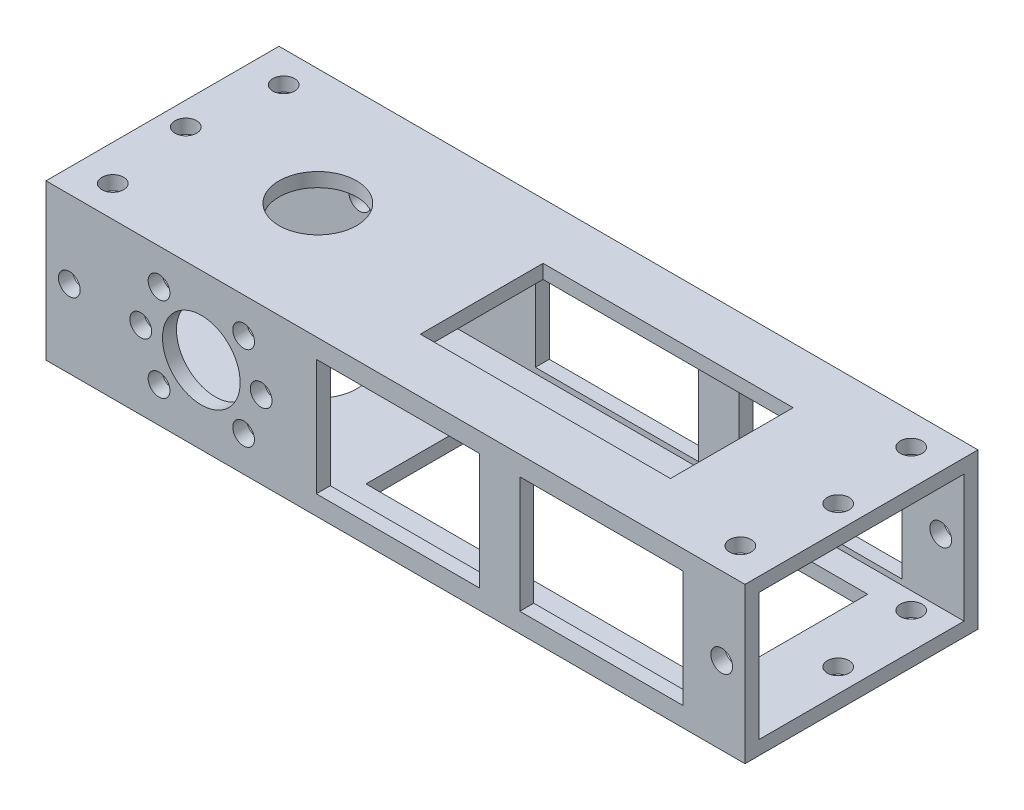
SolidWorks part; units mm, degrees
material "6061-T6 (SS)"
ref_plane "Front Plane" through (0, 0, 0) normal (0, 0, 1) x (1, 0, 0)
ref_plane "Top Plane" through (0, 0, 0) normal (0, 1, 0) x (1, 0, 0)
ref_plane "Right Plane" through (0, 0, 0) normal (1, 0, 0) x (0, 0, -1)
sketch "Sketch1" plane through (0, 0, 0) normal (0, 1, 0) x (1, 0, 0)
  line L1 (0, 0) -> (-114.3, 0)
  line L2 (0, 0) -> (0, -38.1)
  line L3 (0, -38.1) -> (-114.3, -38.1)
  line L4 (-114.3, 0) -> (-114.3, -38.1)
  dimension "D1" = 114.3
  dimension "D2" = 38.1
extrude "Boss-Extrude1" add sketch "Sketch1" along normal blind 25.4
sketch "Sketch2" plane through (0, 0, 0) normal (1, 0, 0) x (0, 0, -1)
  line L0 (0, 0) -> (-2.286, 0) construction
  line L1 (-38.1, 0) -> (0, 0) construction
  line L2 (-2.286, 0) -> (-2.286, 2.286) construction
  line L4 (-2.286, 2.286) -> (-35.814, 2.286)
  line L5 (-2.286, 2.286) -> (-2.286, 23.114)
  line L6 (-2.286, 23.114) -> (-35.814, 23.114)
  line L7 (-35.814, 2.286) -> (-35.814, 23.114)
  line L8 (-38.1, 25.4) -> (-38.1, 0) construction
  point P11 (-38.1, 12.7)
  dimension "D1" = 20.828
  dimension "D2" = 33.528
  dimension "D3" = 2.286
  dimension "D4" = 2.286
extrude "Cut-Extrude1" cut sketch "Sketch2" against normal up to next
sketch "Sketch4" plane through (0, 0, 0) normal (0, 0, -1) x (-1, 0, 0)
  line L0 (0, 0) -> (0, 12.7) construction
  line L1 (0, 25.4) -> (0, 0) construction
  line L2 (0, 12.7) -> (3.81, 12.7) construction
  circle A0 centre (3.81, 12.7) radius 1.778
  dimension "D1" = 3.556
  dimension "D2" = 3.81
extrude "Cut-Extrude3" cut sketch "Sketch4" against normal up to surface (38.1 mm away) up to face at (-57.15, 12.7, 38.1)
sketch "Sketch6" plane through (0, 0, 0) normal (0, 0, -1) x (-1, 0, 0)
  line L0 (114.3, 0) -> (114.3, 12.7) construction
  line L1 (114.3, 25.4) -> (114.3, 0) construction
  line L2 (114.3, 12.7) -> (110.49, 12.7) construction
  line L3 (114.3, 12.7) -> (88.9, 12.7) construction
  line L4 (88.9, 12.7) -> (81.9852, 5.7852) construction
  line L5 (88.9, 12.7) -> (95.8148, 19.6148) construction
  line L6 (88.9, 12.7) -> (95.8148, 5.7852) construction
  line L7 (88.9, 12.7) -> (81.9852, 19.6148) construction
  line L8 (0, 12.7) -> (43.434, 12.7) construction
  line L9 (88.9, 12.7) -> (98.806, 12.7) construction
  line L10 (88.9, 12.7) -> (79.121, 12.7) construction
  line L11 (0, 12.7) -> (10.16, 12.7) construction
  line L12 (0, 25.4) -> (0, 0) construction
  line L13 (10.16, 12.7) -> (10.16, 22.225)
  line L14 (10.16, 22.225) -> (36.83, 22.225)
  line L15 (36.83, 22.225) -> (36.83, 3.175)
  line L16 (36.83, 3.175) -> (10.16, 3.175)
  line L17 (10.16, 3.175) -> (10.16, 12.7)
  line L18 (0, 25.4) -> (114.3, 25.4) construction
  line L19 (43.434, 12.7) -> (43.434, 22.225)
  line L20 (43.434, 22.225) -> (70.104, 22.225)
  line L21 (70.104, 22.225) -> (70.104, 3.175)
  line L22 (70.104, 3.175) -> (43.434, 3.175)
  line L23 (43.434, 3.175) -> (43.434, 12.7)
  circle A0 centre (110.49, 12.7) radius 1.778
  circle A1 centre (88.9, 12.7) radius 6.35
  circle A2 centre (81.9852, 19.6148) radius 1.778
  circle A3 centre (95.8148, 19.6148) radius 1.778
  circle A4 centre (95.8148, 5.7852) radius 1.778
  circle A5 centre (81.9852, 5.7852) radius 1.778
  circle A6 centre (79.121, 12.7) radius 1.778
  circle A7 centre (98.806, 12.7) radius 1.778
  dimension "D1" = 12.7
  dimension "D2" = 3.81
  dimension "D3" = 3.556
  dimension "D5" = 9.779
  dimension "D7" = 9.906
  dimension "D4" = 25.4
  dimension "D6" = 32.3148
  dimension "D8" = 10.16
  dimension "D9" = 26.67
  dimension "D10" = 3.175
  dimension "D11" = 19.05
  dimension "D12" = 43.434
extrude "Cut-Extrude5" cut sketch "Sketch6" against normal up to surface (38.1 mm away) up to face at (-5.588, 12.7, 38.1)
sketch "Sketch7" plane through (0, 25.4, 0) normal (0, 1, 0) x (1, 0, 0)
  line L0 (-114.3, -38.1) -> (-114.3, -19.05) construction
  line L1 (-114.3, 0) -> (-114.3, -38.1) construction
  line L2 (-114.3, -19.05) -> (-110.49, -19.05) construction
  line L3 (-114.3, -19.05) -> (-88.9, -19.05) construction
  line L4 (-88.9, -19.05) -> (-61.976, -19.05) construction
  line L5 (-61.976, -19.05) -> (-61.976, -9.144)
  line L6 (-61.976, -19.05) -> (-61.976, -29.21)
  line L7 (-61.976, -29.21) -> (-21.082, -29.21)
  line L8 (-61.976, -9.144) -> (-21.082, -9.144)
  line L9 (-21.082, -9.144) -> (-21.082, -29.21)
  line L10 (0, -38.1) -> (0, 0) construction
  line L12 (-41.529, -29.21) -> (-41.529, -38.1) construction
  line L13 (-114.3, -38.1) -> (0, -38.1) construction
  line L14 (-114.3, 0) -> (-108.458, 0) construction
  line L15 (0, 0) -> (-114.3, 0) construction
  line L16 (-108.458, 0) -> (-108.458, -5.08) construction
  line L17 (-114.3, -38.1) -> (-108.458, -38.1) construction
  line L18 (-108.458, -38.1) -> (-108.458, -33.02) construction
  circle A0 centre (-110.49, -19.05) radius 1.778
  circle A1 centre (-88.9, -19.05) radius 6.35
  circle A2 centre (-108.458, -5.08) radius 1.778
  circle A3 centre (-108.458, -33.02) radius 1.778
  dimension "D1" = 12.7
  dimension "D3" = 3.556
  dimension "D2" = 3.81
  dimension "D4" = 25.4
  dimension "D5" = 20.066
  dimension "D6" = 40.894
  dimension "D7" = 21.082
  dimension "D8" = 8.89
  dimension "D9" = 5.842
  dimension "D10" = 5.08
extrude "Cut-Extrude6" cut sketch "Sketch7" against normal up to next
sketch "Sketch8" plane through (0, 0, 0) normal (0, -1, 0) x (1, 0, 0)
  line L0 (-114.3, 38.1) -> (-114.3, 19.05) construction
  line L1 (-114.3, 0) -> (-114.3, 38.1) construction
  line L2 (-114.3, 19.05) -> (-110.49, 19.05) construction
  line L3 (-114.3, 19.05) -> (-88.9, 19.05) construction
  line L4 (-88.9, 19.05) -> (-68.326, 19.05) construction
  line L5 (-68.326, 19.05) -> (-68.326, 31.75)
  line L6 (-68.326, 19.05) -> (-68.326, 6.35)
  line L7 (-68.326, 31.75) -> (-11.684, 31.75)
  line L8 (-68.326, 6.35) -> (-11.684, 6.35)
  line L9 (-11.684, 6.35) -> (-11.684, 31.75)
  line L10 (-114.3, 0) -> (-108.458, 0) construction
  line L11 (0, 0) -> (-114.3, 0) construction
  line L12 (-114.3, 38.1) -> (0, 38.1) construction
  line L13 (-40.005, 31.75) -> (-40.005, 38.1) construction
  line L14 (-68.326, 19.05) -> (-68.326, 38.1) construction
  line L15 (-108.458, 0) -> (-108.458, 5.08) construction
  line L16 (-114.3, 38.1) -> (-108.458, 38.1) construction
  line L17 (-108.458, 38.1) -> (-108.458, 33.02) construction
  circle A0 centre (-110.49, 19.05) radius 1.778
  circle A1 centre (-88.9, 19.05) radius 6.35
  circle A2 centre (-108.458, 33.02) radius 1.778
  circle A3 centre (-108.458, 5.08) radius 1.778
  dimension "D1" = 12.7
  dimension "D4" = 3.556
  dimension "D8" = 20.574
  dimension "D2" = 56.642
  dimension "D3" = 25.4
  dimension "D5" = 3.81
  dimension "D6" = 25.4
  dimension "D7" = 6.35
  dimension "D9" = 19.05
  dimension "D10" = 5.842
  dimension "D11" = 5.08
extrude "Cut-Extrude7" cut sketch "Sketch8" against normal up to next
sketch "Sketch10" plane through (0, 0, 0) normal (0, -1, 0) x (-1, 0, 0)
  line L0 (0, -38.1) -> (0, -19.05) construction
  line L1 (0, -38.1) -> (0, 0) construction
  line L2 (0, -19.05) -> (3.81, -19.05) construction
  line L3 (0, -38.1) -> (5.842, -38.1) construction
  line L4 (114.3, -38.1) -> (0, -38.1) construction
  line L5 (5.842, -38.1) -> (5.842, -33.02) construction
  line L6 (0, 0) -> (5.842, 0) construction
  line L7 (0, 0) -> (114.3, 0) construction
  line L8 (5.842, 0) -> (5.842, -5.08) construction
  circle A0 centre (3.81, -19.05) radius 1.778
  circle A1 centre (5.842, -33.02) radius 1.778
  circle A2 centre (5.842, -5.08) radius 1.778
  dimension "D1" = 3.556
  dimension "D3" = 5.842
  dimension "D2" = 5.08
  dimension "D4" = 3.81
extrude "Cut-Extrude9" cut sketch "Sketch10" against normal up to surface (25.4 mm away) up to face at (-108.458, 25.4, 34.798)
